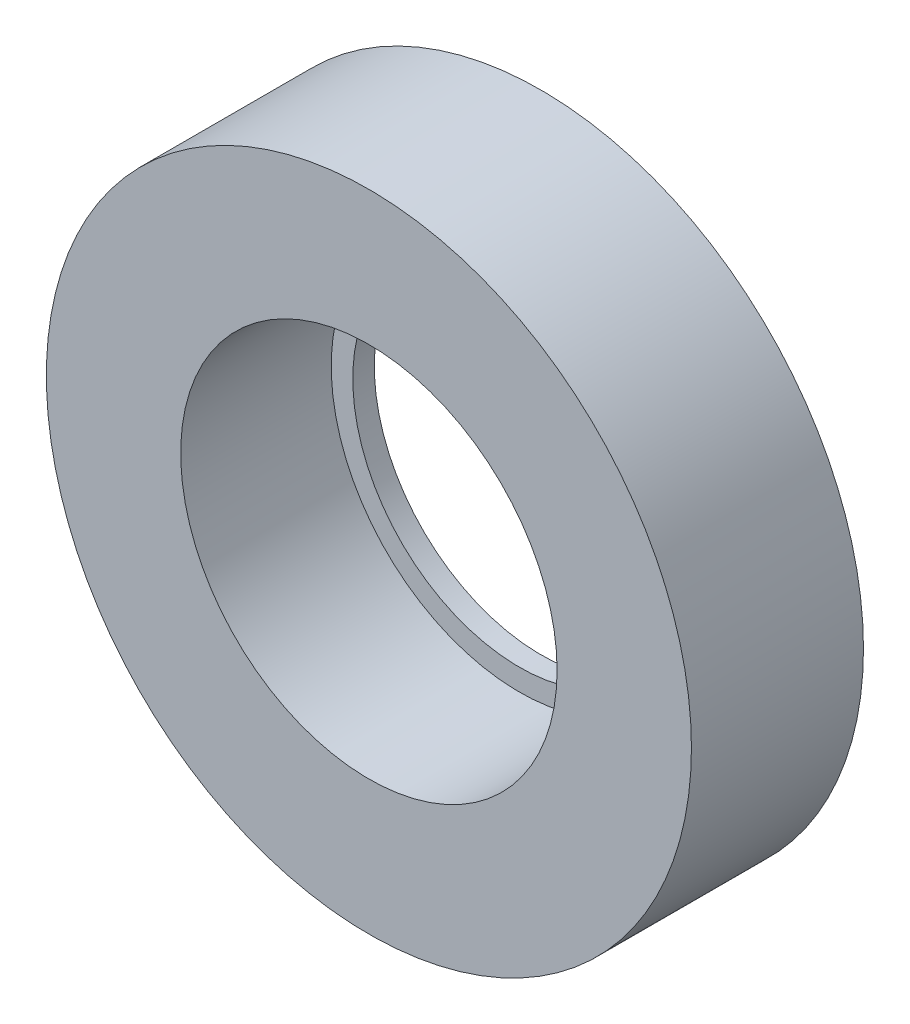
SolidWorks part; units mm, degrees
ref_plane "Front Plane" through (0, 0, 0) normal (0, 0, 1) x (1, 0, 0)
ref_plane "Top Plane" through (0, 0, 0) normal (0, 1, 0) x (1, 0, 0)
ref_plane "Right Plane" through (0, 0, 0) normal (1, 0, 0) x (0, 0, -1)
sketch "Sketch1" plane through (0, 0, 0) normal (0, 0, 1) x (1, 0, 0)
  circle A0 centre (0, 0) radius 30
extrude "Boss-Extrude1" add sketch "Sketch1" along normal blind 16
sketch "Sketch2" plane through (0, 0, 16) normal (0, 0, 1) x (1, 0, 0)
  circle A0 centre (0, 0) radius 17.505
extrude "Cut-Extrude1" cut sketch "Sketch2" against normal blind 14
sketch "Sketch4" plane through (0, 0, 2) normal (0, 0, 1) x (1, 0, 0)
  circle A0 centre (0, 0) radius 15.5
extrude "Cut-Extrude2" cut sketch "Sketch4" against normal through all
